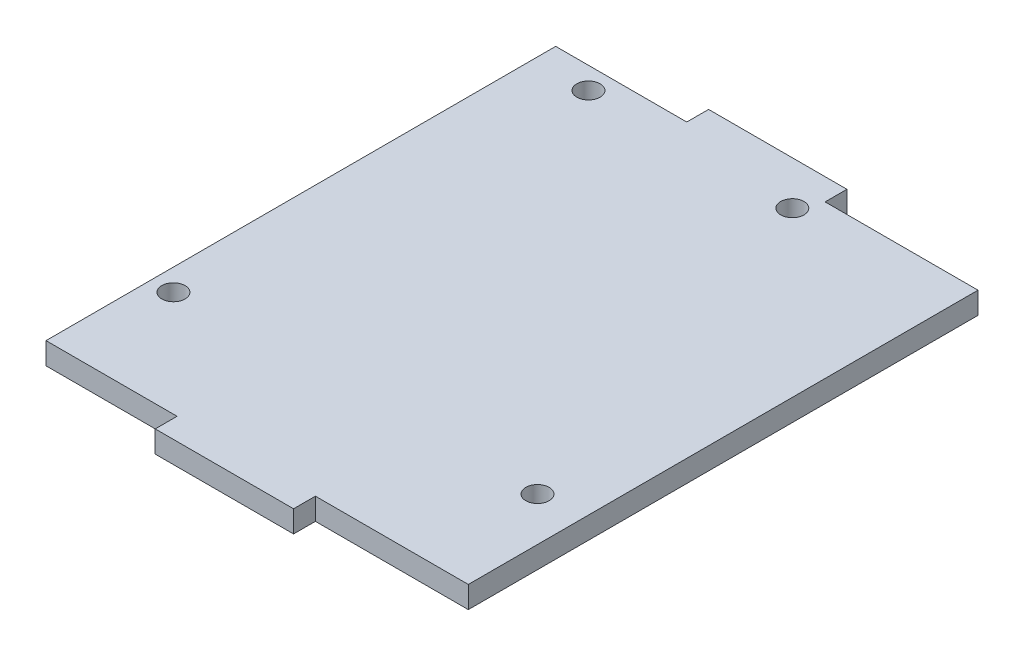
SolidWorks part; units mm, degrees
ref_plane "Front Plane" through (0, 0, 0) normal (0, 0, 1) x (1, 0, 0)
ref_plane "Top Plane" through (0, 0, 0) normal (0, 1, 0) x (1, 0, 0)
ref_plane "Right Plane" through (0, 0, 0) normal (1, 0, 0) x (0, 0, -1)
sketch "Sketch1" plane through (0, 0, 0) normal (0, 1, 0) x (1, 0, 0)
  line L2 (3, 7) -> (3, 21)
  line L6 (57.5, 34.5) -> (57.5, -34.5)
  line L7 (3, 35) -> (21, 35)
  line L8 (21, 35) -> (21, 38)
  line L9 (21, 38) -> (40, 38)
  line L10 (40, 38) -> (40, 35)
  line L11 (40, 35) -> (58, 35)
  line L12 (3.5, -34.5) -> (57.5, -34.5)
  line L13 (0, 0) -> (58, 0) construction
  line L14 (61, 21) -> (61, -21)
  line L15 (3, 35) -> (3, -35)
  line L17 (61, -21) -> (61, -35)
  line L18 (61, -35) -> (58, -35)
  line L19 (61, 35) -> (58, 35)
  line L23 (3, -7) -> (3, -21)
  line L25 (30.5, -34.5) -> (30.5, 34.5) construction
  line L26 (61, 21) -> (61, 35)
  line L27 (3.5, 34.5) -> (57.5, 34.5)
  line L28 (3.5, 34.5) -> (3.5, -34.5)
  line L29 (3.5, -34.5) -> (57.5, -34.5)
  line L30 (57.5, 34.5) -> (57.5, -34.5)
  line L31 (3.5, 34.5) -> (57.5, -34.5) construction
  line L32 (3.5, -34.5) -> (57.5, 34.5) construction
  line L37 (61, -35) -> (58, -35)
  line L38 (40, -35) -> (58, -35)
  line L39 (40, -38) -> (40, -35)
  line L40 (21, -38) -> (40, -38)
  line L41 (21, -35) -> (21, -38)
  line L42 (3, -35) -> (21, -35)
  circle A0 centre (6, -20.5) radius 1.6
  circle A1 centre (55, -19.5) radius 1.6
  circle A2 centre (10.5, 32) radius 1.6
  circle A3 centre (38.5, 32) radius 1.6
  point P29 (30.5, 0)
  dimension "D14" = 3.2
  dimension "D17" = 3.2
  dimension "D18" = 3.2
  dimension "D19" = 3.2
  dimension "D2" = 14
  dimension "D4" = 19
  dimension "D5" = 18
  dimension "D6" = 54
  dimension "D7" = 18
  dimension "D10" = 14
  dimension "D11" = 3
  dimension "D12" = 69
  dimension "D13" = 2.5
  dimension "D15" = 2.5
  dimension "D16" = 15
  dimension "D20" = 7
  dimension "D21" = 2.5
  dimension "D22" = 2.5
  dimension "D23" = 19
extrude "Boss-Extrude1" add sketch "Sketch1" along normal blind 3 contours L42 L41 L40 L39 L38 L18 L17 L26 L19 L11 L10 L9 L8 L7 L2 L23 L28 L27 L6 L12 | L27 L28 L12 L6 A3 A2 A1 A0 region at (3.0956, 0, -14) region at (30.5261, 0, 0.0523)
